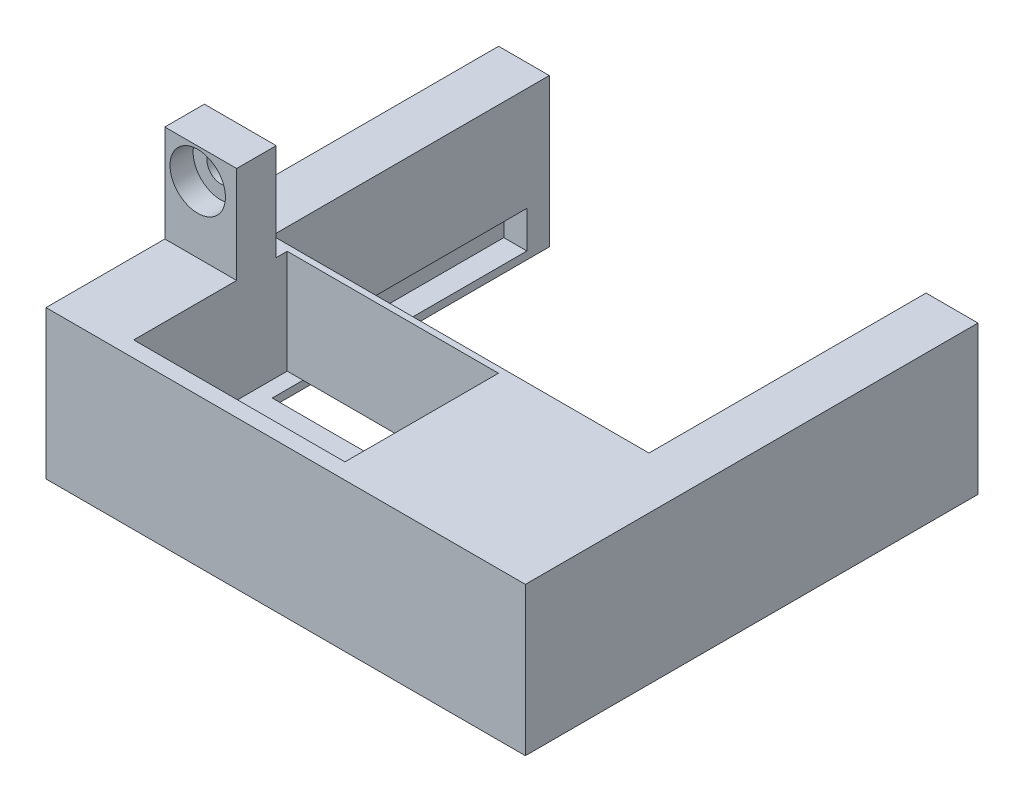
SolidWorks part; units mm, degrees
ref_plane "Front Plane" through (0, 0, 0) normal (0, 0, 1) x (1, 0, 0)
ref_plane "Top Plane" through (0, 0, 0) normal (0, 1, 0) x (1, 0, 0)
ref_plane "Right Plane" through (0, 0, 0) normal (1, 0, 0) x (0, 0, -1)
sketch "Sketch2" plane through (0, 0, 0) normal (0, 0, 1) x (1, 0, 0)
  line L1 (-53.8027, 16.2378) -> (-1.9068, 16.2378)
  line L2 (-53.8027, 16.2378) -> (-53.8027, 0.1683)
  line L3 (-53.8027, 0.1683) -> (-1.9068, 0.1683)
  line L4 (-1.9068, 16.2378) -> (-1.9068, 0.1683)
  line L5 (-53.8027, 16.2378) -> (-1.9068, 0.1683) construction
  line L6 (-53.8027, 0.1683) -> (-1.9068, 16.2378) construction
  point P0 (-6.1394, 14.9272)
  point P6 (0, 0)
  point P7 (0, 0)
extrude "Boss-Extrude1" add sketch "Sketch2" along normal blind 49
sketch "Sketch3" plane through (0, 0, 0) normal (0, 0, -1) x (-1, 0, 0)
  line L0 (1.9068, 16.2378) -> (53.8027, 16.2378) construction
  line L1 (7.527, 16.2378) -> (48.316, 16.2378)
  line L2 (7.527, 16.2378) -> (7.527, 0.1683)
  line L3 (7.527, 0.1683) -> (48.316, 0.1683)
  line L4 (48.316, 16.2378) -> (48.316, 0.1683)
  line L5 (53.8027, 0.1683) -> (1.9068, 0.1683) construction
extrude "Cut-Extrude1" cut sketch "Sketch3" against normal blind 30 contours L4 L3 L2 L1
sketch "Sketch4" plane through (0, 16.2378, 0) normal (0, 1, 0) x (1, 0, 0)
  line L1 (-46.0238, -30.6644) -> (-23.154, -30.6644)
  line L2 (-46.0238, -30.6644) -> (-46.0238, -47.2844)
  line L3 (-46.0238, -47.2844) -> (-23.154, -47.2844)
  line L4 (-23.154, -30.6644) -> (-23.154, -47.2844)
  point P4 (0, 0)
extrude "Cut-Extrude2" cut sketch "Sketch4" against normal blind 14 contours L2 L3 L4 L1
sketch "Sketch5" plane through (-7.527, 0, 0) normal (-1, 0, 0) x (0, 0, 1)
  line L1 (4, 5) -> (30, 5)
  line L2 (4, 5) -> (4, 1)
  line L3 (4, 1) -> (30, 1)
  line L4 (30, 5) -> (30, 1)
  line L6 (30, 16.2378) -> (30, 0.1683) construction
  point P4 (0, 0)
  point P5 (30, 1.0636)
  point P8 (0, 0)
  point P9 (30, 1.07)
  point P10 (30, 1.0687)
  point P11 (30, 1.0686)
  point P12 (30, 1.0687)
extrude "Cut-Extrude3" cut sketch "Sketch5" against normal blind 2.5
sketch "Sketch12" plane through (-48.316, 0, 0) normal (1, 0, 0) x (0, 0, -1)
  line L1 (-2.4245, 5) -> (-30, 5)
  line L2 (-2.4245, 5) -> (-2.4245, 1)
  line L3 (-2.4245, 1) -> (-30, 1)
  line L4 (-30, 5) -> (-30, 1)
  line L5 (-30, 16.2378) -> (-30, 0.1683) construction
  point P6 (0, 0)
  point P8 (-4.225, 1.0588)
  point P9 (-4.2026, 1.0686)
extrude "Cut-Extrude6" cut sketch "Sketch12" against normal blind 2.5
sketch "Sketch15" plane through (0, 0, 30) normal (0, 0, -1) x (-1, 0, 0)
  line L1 (5.027, 5) -> (50.816, 5)
  line L2 (5.027, 5) -> (5.027, 1)
  line L3 (5.027, 1) -> (50.816, 1)
  line L4 (50.816, 5) -> (50.816, 1)
extrude "Cut-Extrude7" cut sketch "Sketch15" against normal blind 17.5
sketch "Sketch17" plane through (0, 16.2378, 0) normal (0, 1, 0) x (1, 0, 0)
  line L0 (-53.8027, -49) -> (-53.8027, 0) construction
  line L1 (-53.8027, -31.8535) -> (-46.0238, -31.8535)
  line L2 (-53.8027, -31.8535) -> (-53.8027, -36.1385)
  line L3 (-53.8027, -36.1385) -> (-46.0238, -36.1385)
  line L4 (-46.0238, -31.8535) -> (-46.0238, -36.1385)
  line L5 (-46.0238, -30.6644) -> (-46.0238, -47.2844) construction
extrude "Boss-Extrude2" add sketch "Sketch17" along normal blind 10.5
sketch "Sketch18" plane through (0, 0, 36.1385) normal (0, 0, 1) x (1, 0, 0)
  circle A0 centre (-50.2396, 23.4298) radius 1.5
extrude "Cut-Extrude8" cut sketch "Sketch18" against normal blind 5 contours A0
sketch "Sketch19" plane through (0, 0, 36.1385) normal (0, 0, 1) x (1, 0, 0)
  circle A0 centre (-50.2396, 23.4298) radius 3
extrude "Cut-Extrude9" cut sketch "Sketch19" against normal blind 2.5 contours A0
